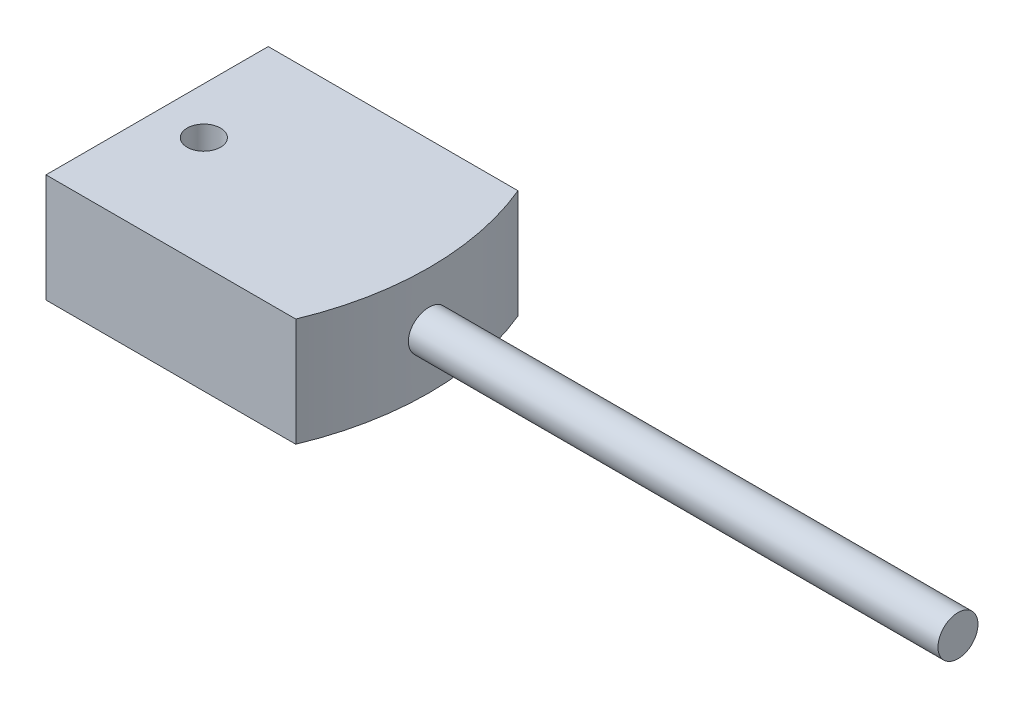
SolidWorks part; units mm, degrees
ref_plane "Front Plane" through (0, 0, 0) normal (0, 0, 1) x (1, 0, 0)
ref_plane "Top Plane" through (0, 0, 0) normal (0, 1, 0) x (1, 0, 0)
ref_plane "Right Plane" through (0, 0, 0) normal (1, 0, 0) x (0, 0, -1)
sketch "Sketch1" plane through (0, 0, 0) normal (0, 1, 0) x (1, 0, 0)
  line L0 (0, 0) -> (17.6424, 0) construction
  line L1 (0, 8.4582) -> (19.0109, 8.4582)
  line L2 (0, 8.4582) -> (0, -8.4582)
  line L3 (0, -8.4582) -> (19.0109, -8.4582)
  line L4 (19.0109, 8.4582) -> (19.0109, -8.4582) construction
  arc A0 (19.0109, 8.4582) -> (19.0109, -8.4582) centre (-1.309, 0) cw
  circle A1 centre (3.556, 0) radius 1.27
  dimension "D3" = 2.54
  dimension "D1" = 20.701
  dimension "D2" = 16.9164
  dimension "D4" = 3.556
  dimension "D5" = 3.3802
extrude "Boss-Extrude1" add sketch "Sketch1" along normal blind 4.1275 and the other way blind 4.1275
ref_axis "Axis1" through (21.736, 0, 0) along (-1, 0, 0)
sketch "Sketch2" plane through (0, 0, 0) normal (0, 1, 0) x (1, 0, 0)
  line L0 (21.736, 0) -> (-1.035, 0) construction
  line L1 (20.701, 0) -> (60.96, 0)
  line L2 (20.701, 0) -> (20.701, 1.524) construction
  line L3 (20.701, 1.524) -> (60.96, 1.524)
  line L4 (60.96, 0) -> (60.96, 1.524)
  line L5 (20.701, 1.524) -> (20.0169, 1.524)
  line L6 (20.701, 1.524) -> (20.701, 0) construction
  line L7 (20.701, 0) -> (20.0169, 0)
  line L8 (20.0169, 1.524) -> (20.0169, 0)
  arc A0 (19.0109, -8.4582) -> (19.0109, 8.4582) centre (-1.309, 0) ccw construction
  dimension "D1" = 40.259
  dimension "D2" = 1.524
  dimension "D3" = 0.6841
revolve "Revolve1" add sketch "Sketch2" angle 360 about axis through (21.736, 0, 0) along (-1, 0, 0)
